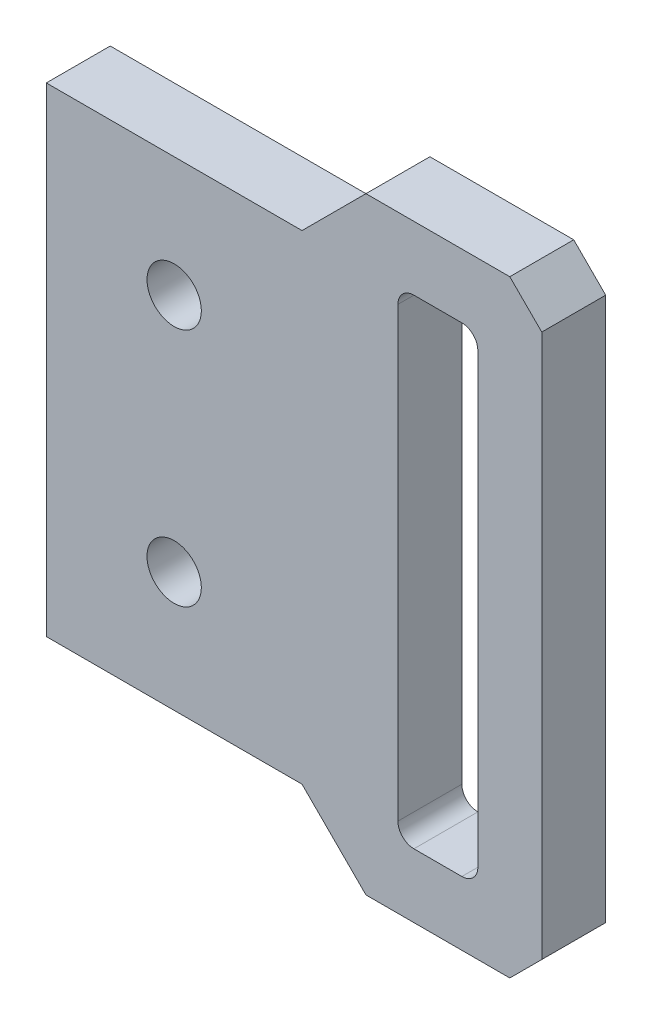
SolidWorks part; units mm, degrees
other "Markup1"
sketch "Sketch3" plane through (7.0191, 23.3872, 4) normal (0.0694, 0.1001, 0.9926) x (0.9941, 0.0764, -0.0772)
other "Markup2"
sketch "Sketch4" plane through (7.0191, 23.3872, 4) normal (0.4538, 0.89, 0.0453) x (0.1814, -0.0426, -0.9825)
ref_plane "Front Plane" through (0, 0, 0) normal (0, 0, 1) x (1, 0, 0)
ref_plane "Top Plane" through (0, 0, 0) normal (0, 1, 0) x (1, 0, 0)
ref_plane "Right Plane" through (0, 0, 0) normal (1, 0, 0) x (0, 0, -1)
sketch "Sketch1" plane through (0, 0, 0) normal (0, 0, 1) x (1, 0, 0)
  line L0 (-2.5, -15) -> (-2.5, 15)
  line L1 (6.5, -19) -> (-6.5, -19)
  line L2 (6.5, -19) -> (6.5, 19)
  line L3 (6.5, 19) -> (-6.5, 19)
  line L4 (-6.5, -19) -> (-6.5, 19)
  line L5 (6.5, -19) -> (-6.5, 19) construction
  line L6 (6.5, 19) -> (-6.5, -19) construction
  line L7 (2.5, 15) -> (-2.5, 15)
  line L8 (2.5, -15) -> (2.5, 15)
  line L9 (2.5, -15) -> (-2.5, -15)
  point P0 (0, 0)
  dimension "D1" = 5
  dimension "D2" = 30
  dimension "D3" = 38
extrude "Boss-Extrude1" add sketch "Sketch1" along normal blind 4
chamfer "Chamfer1" distance 2 angle 45 4 edges at (-6.5, 19, 2) (6.5, -19, 2) (-6.5, -19, 2) (6.5, 19, 2)
fillet "Fillet1" [suppressed] radius 2
ref_plane "Plane1" through (0, 0, 2) normal (0, 0, 1) x (1, 0, 0)
sketch "Sketch2" plane through (0, 0, 2) normal (0, 0, 1) x (1, 0, 0)
  line L0 (-6.5, 17) -> (-8.5, 15)
  line L1 (-6.5, 17) -> (-6.5, -17) construction
  line L2 (-8.5, 15) -> (-24.5, 15)
  line L3 (-24.5, 15) -> (-24.5, -15)
  line L4 (-24.5, -15) -> (-8.5, -15)
  line L5 (-8.5, -15) -> (-6.5, -17)
  line L6 (-6.5, 17) -> (-6.5, -17)
  line L7 (-4.5, 19) -> (-6.5, 17) construction
  line L8 (-16.5, 7.5) -> (-16.5, -7.5) construction
  line L9 (-27.0514, 15) -> (-27.0514, 7.5) construction
  line L10 (-27.0514, 7.5) -> (-27.0514, 0) construction
  line L11 (-27.0514, 0) -> (-27.0514, -7.5) construction
  line L12 (-27.0514, -7.5) -> (-27.0514, -15) construction
  line L13 (-8.5, 15) -> (-8.5, -15) construction
  line L14 (-8.5, 0) -> (-24.5, 0) construction
  line L15 (2.5, 15) -> (-2.5, 15) construction
  circle A0 centre (-16.5, 7.5) radius 1.7
  circle A1 centre (-16.5, -7.5) radius 1.7
  point P2 (-6.5, 0)
  point P4 (-24.5, 0)
  point P21 (-16.5, 0)
  dimension "D1" = 3.4
  dimension "D2" = 18
extrude "Boss-Extrude2" add sketch "Sketch2" along normal blind 2 and the other way blind 2
fillet "Fillet2" radius 1 4 edges at (2.5, -15, 2) (-2.5, -15, 2) (2.5, 15, 2) (-2.5, 15, 2)
equation "\"slot_w\"=0.005000"
equation "\"slot_h\"=0.030000"
equation "\"t\"=0.004000"
equation "\"height\"=0.038000"
equation "\"hole_D\"=0.003400"
equation "\"attach_w\"=0.018000"
equation "\"D1@Sketch1\"=\"slot_w\"*1000"
equation "\"D2@Sketch1\"=\"slot_h\"*1000"
equation "\"D3@Sketch1\"=\"height\"*1000"
equation "\"D1@Sketch2\"=\"hole_D\"*1000"
equation "\"D2@Sketch2\"=\"attach_w\"*1000"
